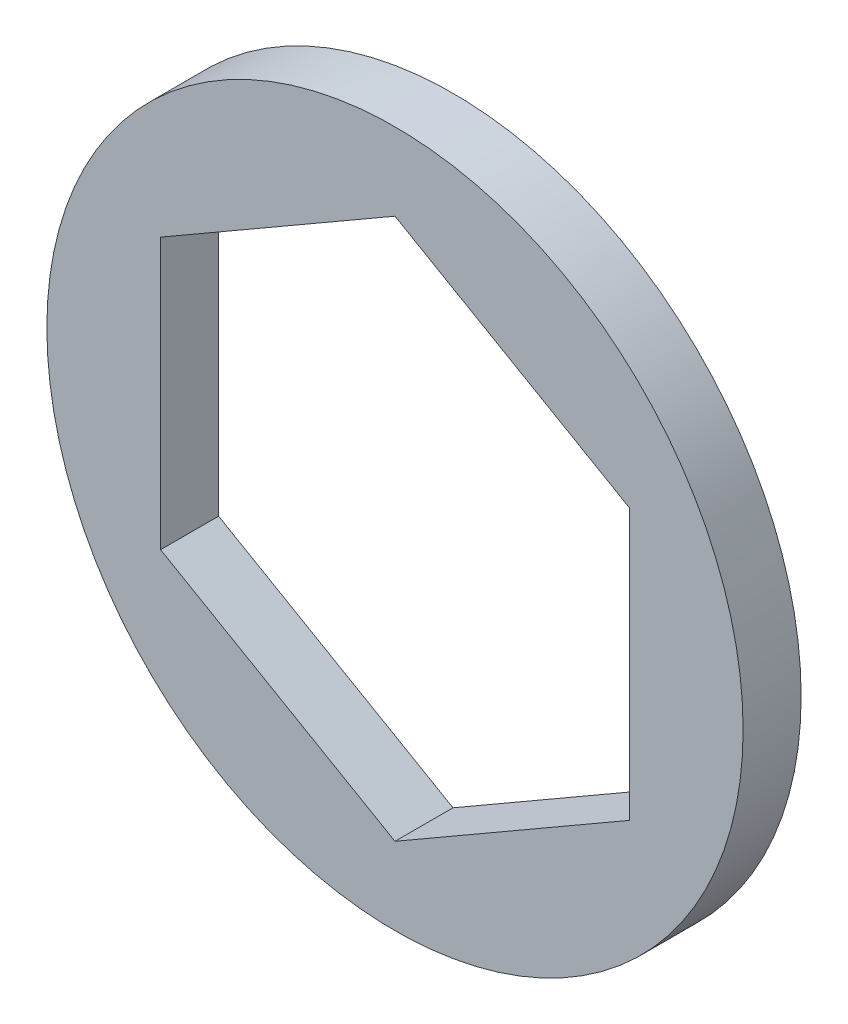
SolidWorks part; units mm, degrees
material "PET"
ref_plane "Front Plane" through (0, 0, 0) normal (0, 0, 1) x (1, 0, 0)
ref_plane "Top Plane" through (0, 0, 0) normal (0, 1, 0) x (1, 0, 0)
ref_plane "Right Plane" through (0, 0, 0) normal (1, 0, 0) x (0, 0, -1)
sketch "Sketch2" plane through (0, 0, 0) normal (0, 0, 1) x (1, 0, 0)
  line L1 (6.4135, 3.7028) -> (0, 7.4057)
  line L2 (0, 7.4057) -> (-6.4135, 3.7028)
  line L3 (-6.4135, 3.7028) -> (-6.4135, -3.7028)
  line L4 (-6.4135, -3.7028) -> (0, -7.4057)
  line L5 (0, -7.4057) -> (6.4135, -3.7028)
  line L6 (6.4135, -3.7028) -> (6.4135, 3.7028)
  circle A0 centre (0, 0) radius 9.525
  circle A1 centre (0, 0) radius 6.4135 construction
  point P3 (0, 0)
  point P11 (0, 7.3323)
  point P12 (0, 0)
  point P13 (0, 0)
  dimension "D1" = 12.827
  dimension "D2" = 19.05
extrude "Boss-Extrude1" add sketch "Sketch2" along normal blind 1.5875
